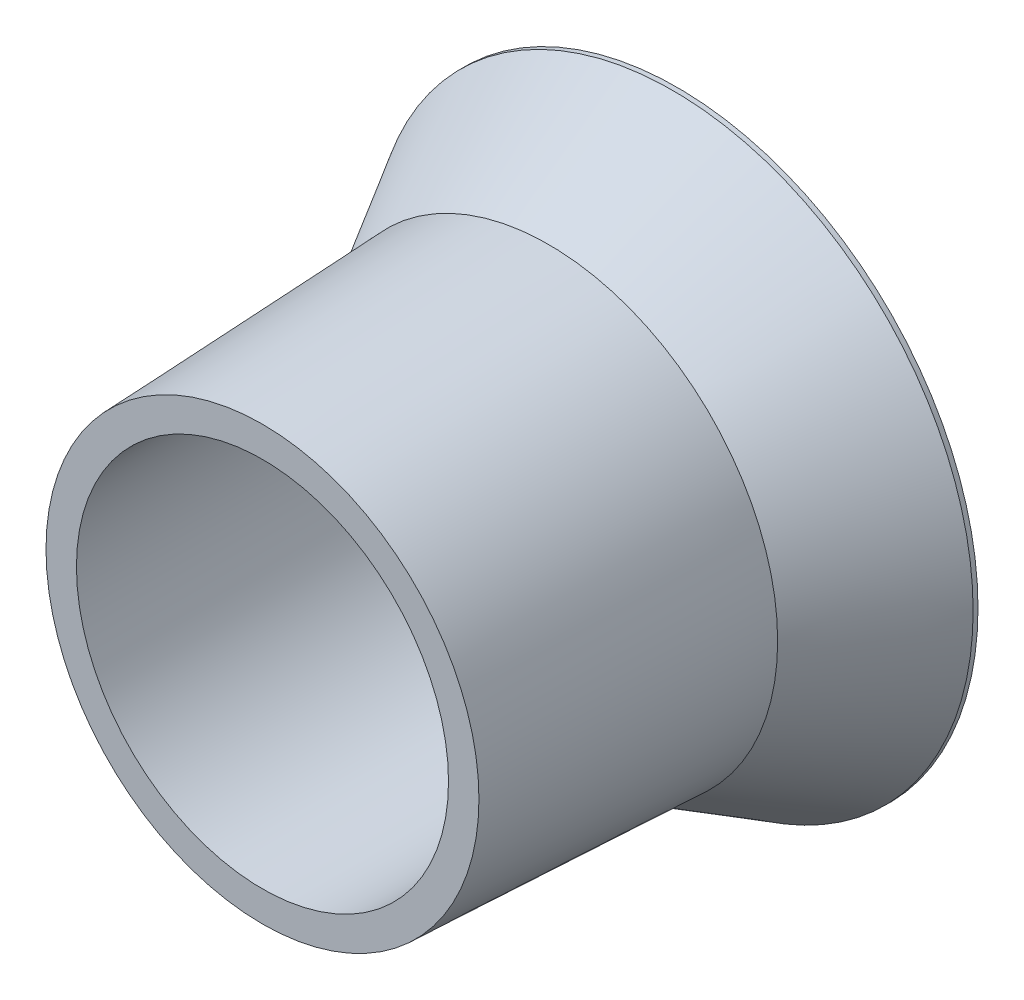
SolidWorks part; units mm, degrees
ref_plane "Front Plane" through (0, 0, 0) normal (0, 0, 1) x (1, 0, 0)
ref_plane "Top Plane" through (0, 0, 0) normal (0, 1, 0) x (1, 0, 0)
ref_plane "Right Plane" through (0, 0, 0) normal (1, 0, 0) x (0, 0, -1)
sketch "Sketch1" plane through (0, 0, 0) normal (0, 0, 1) x (1, 0, 0)
  circle A0 centre (0, 0) radius 40
  circle A1 centre (0, 0) radius 32.5
  dimension "D1" = 80
  dimension "D2" = 7.5
extrude "Boss-Extrude1" add sketch "Sketch1" along normal blind 50
chamfer "Chamfer1" distance 50 angle 2.5 1 edges at (40, 0, 50) first distance on face at (40, 0, 50)
sketch "Sketch2" plane through (0, 0, 0) normal (0, 0, -1) x (-1, 0, 0)
  circle A0 centre (0, 0) radius 52.5
  circle A1 centre (0, 0) radius 32.5 construction
  circle A2 centre (0, 0) radius 32.5
  dimension "D1" = 105
extrude "Boss-Extrude2" add sketch "Sketch2" along normal blind 22.5
chamfer "Chamfer2" distance 12.5 angle 60 1 edges at (-52.5, 0, 0) first distance on face at (-40, 0, 0)
